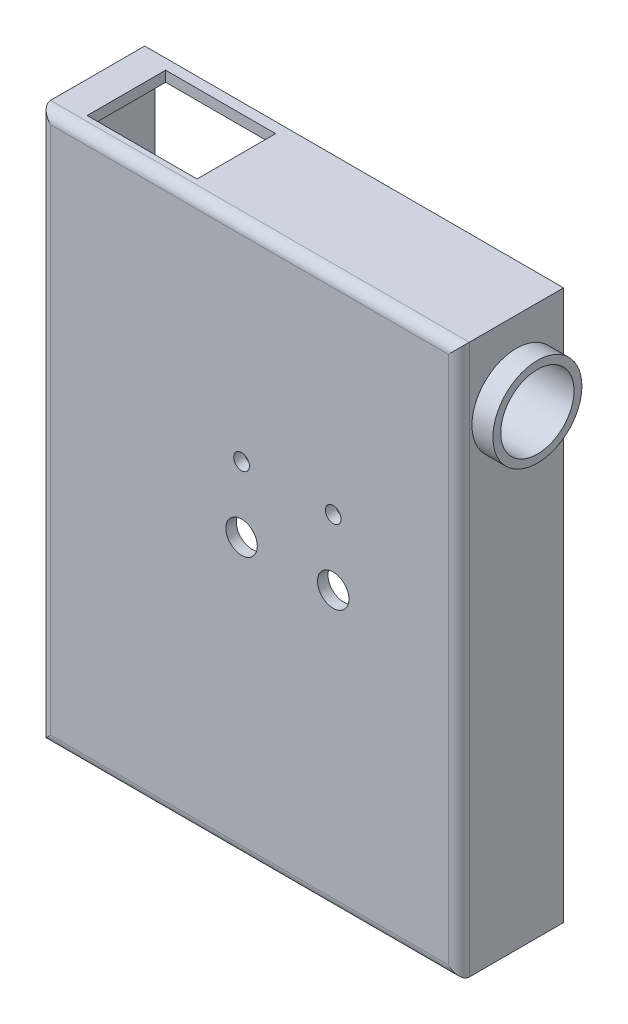
SolidWorks part; units mm, degrees
ref_plane "Front Plane" through (0, 0, 0) normal (0, 0, 1) x (1, 0, 0)
ref_plane "Top Plane" through (0, 0, 0) normal (0, 1, 0) x (1, 0, 0)
ref_plane "Right Plane" through (0, 0, 0) normal (1, 0, 0) x (0, 0, -1)
sketch "Sketch1" plane through (0, 0, 0) normal (0, 0, 1) x (1, 0, 0)
  line L9 (1031.5139, -1366.2512) -> (1111.5139, -1366.2512)
  line L10 (1031.5139, -1366.2512) -> (1031.5139, -1471.2512)
  line L11 (1031.5139, -1471.2512) -> (1111.5139, -1471.2512)
  line L12 (1111.5139, -1366.2512) -> (1111.5139, -1471.2512)
  line L13 (1043.5139, -1392.2512) -> (1103.5139, -1392.2512)
  line L14 (1043.5139, -1392.2512) -> (1043.5139, -1467.2512)
  line L15 (1043.5139, -1467.2512) -> (1103.5139, -1467.2512)
  line L16 (1103.5139, -1392.2512) -> (1103.5139, -1467.2512)
  line L17 (1109.5139, -1368.2512) -> (1033.5139, -1368.2512)
  line L18 (1109.5139, -1368.2512) -> (1109.5139, -1469.2512)
  line L19 (1109.5139, -1469.2512) -> (1033.5139, -1469.2512)
  line L20 (1033.5139, -1368.2512) -> (1033.5139, -1469.2512)
  circle A0 centre (1087.5139, -1418.2512) radius 3
  circle A1 centre (1070.0139, -1418.2512) radius 3
  circle A2 centre (1087.5139, -1405.7512) radius 1.5
  circle A3 centre (1070.0139, -1405.7512) radius 1.5
  dimension "D7" = 6
  dimension "D8" = 6
  dimension "D12" = 3
  dimension "D13" = 3
  dimension "D1" = 105
  dimension "D2" = 80
  dimension "D3" = 75
  dimension "D4" = 60
  dimension "D5" = 12
  dimension "D6" = 4
  dimension "D9" = 16
  dimension "D10" = 17.5
  dimension "D11" = 26
  dimension "D14" = 12.5
  dimension "D15" = 12.5
  dimension "D16" = 26
  dimension "D17" = 8
  dimension "D18" = 2
  dimension "D19" = 2
  dimension "D20" = 2
  dimension "D21" = 2
extrude "Boss-Extrude1" add sketch "Sketch1" along normal blind 20 contours L9 L12 L11 L10
extrude "Cut-Extrude4" cut sketch "Sketch1<3>" against normal blind 20 and the other way blind 20 contours A0 | A2 | A3 | A1 region at (1087.5139, -1418.2512, 0)
sketch "Sketch1<3>" plane through (0, 0, 0) normal (0, 0, 1) x (1, 0, 0) same geometry as "Sketch1"
sketch "Sketch2" plane through (0, 0, 0) normal (0, 0, -1) x (-1, 0, 0)
  line L0 (-1111.5139, -1366.2512) -> (-1111.5139, -1471.2512) construction
  line L1 (-1109.5139, -1368.2512) -> (-1033.5139, -1368.2512)
  line L2 (-1109.5139, -1368.2512) -> (-1109.5139, -1469.2512)
  line L3 (-1109.5139, -1469.2512) -> (-1033.5139, -1469.2512)
  line L4 (-1033.5139, -1368.2512) -> (-1033.5139, -1469.2512)
  line L5 (-1031.5139, -1366.2512) -> (-1111.5139, -1366.2512) construction
  line L6 (-1031.5139, -1366.2512) -> (-1031.5139, -1471.2512) construction
  line L7 (-1031.5139, -1471.2512) -> (-1111.5139, -1471.2512) construction
  dimension "D1" = 2
  dimension "D2" = 2
  dimension "D3" = 2
  dimension "D4" = 2
extrude "Cut-Extrude5" cut sketch "Sketch2" against normal blind 18
sketch "Sketch3" plane through (1109.5139, 0, 0) normal (-1, 0, 0) x (0, 0, 1)
  line L0 (0, -1368.2512) -> (0, -1469.2512) construction
  line L1 (18, -1368.2512) -> (0, -1368.2512) construction
  circle A0 centre (9, -1380.2512) radius 6.5
  dimension "D1" = 13
  dimension "D2" = 9
  dimension "D3" = 12
extrude "Cut-Extrude6" cut sketch "Sketch3" against normal blind 18
sketch "Sketch5" plane through (1111.5139, 0, 0) normal (1, 0, 0) x (0, 0, -1)
  circle A0 centre (-9, -1380.2512) radius 8.5
  circle A1 centre (-9, -1380.2512) radius 6.5 construction
  dimension "D1" = 17
  dimension "D2" = 0
  dimension "D3" = 0
extrude "Boss-Extrude2" add sketch "Sketch5" along normal blind 4
sketch "Sketch6" plane through (1109.5139, 0, 0) normal (-1, 0, 0) x (0, 0, 1)
  circle A0 centre (9, -1380.2512) radius 8.5
  circle A1 centre (9, -1380.2512) radius 6.5 construction
  dimension "D1" = 17
  dimension "D2" = 0
extrude "Boss-Extrude3" add sketch "Sketch6" along normal blind 4
sketch "Sketch7" plane through (1115.5139, 0, 0) normal (1, 0, 0) x (0, 0, -1)
  circle A0 centre (-9, -1380.2512) radius 7
  circle A3 centre (-9, -1380.2512) radius 8.5 construction
  dimension "D1" = 14
  dimension "D2" = 0
extrude "Cut-Extrude7" cut sketch "Sketch7" against normal blind 24
sketch "Sketch8" plane through (0, 0, 18) normal (0, 0, -1) x (-1, 0, 0)
  line L0 (-1033.5139, -1368.2512) -> (-1109.5139, -1368.2512) construction
  line L1 (-1102.0139, -1388.2512) -> (-1072.0139, -1388.2512)
  line L2 (-1102.0139, -1388.2512) -> (-1102.0139, -1389.7512)
  line L3 (-1102.0139, -1389.7512) -> (-1072.0139, -1389.7512)
  line L4 (-1072.0139, -1388.2512) -> (-1072.0139, -1389.7512)
  line L5 (-1109.5139, -1368.2512) -> (-1109.5139, -1469.2512) construction
  dimension "D1" = 20
  dimension "D2" = 1.5
  dimension "D3" = 7.5
  dimension "D4" = 30
extrude "Boss-Extrude4" add sketch "Sketch8" along normal blind 14
sketch "Sketch9" plane through (0, -1469.2512, 0) normal (0, 1, 0) x (1, 0, 0)
  line L0 (1109.5139, 0) -> (1033.5139, 0) construction
  line L1 (1109.5139, -18) -> (1109.5139, 0) construction
  circle A0 centre (1071.5139, 0) radius 2.5
  dimension "D2" = 5
  dimension "D1" = 0
  dimension "D3" = 38
extrude "Cut-Extrude8" cut sketch "Sketch9" against normal blind 14
sketch "Sketch10" plane through (0, -1366.2512, 0) normal (0, 1, 0) x (1, 0, 0)
  line L0 (1031.5139, -20) -> (1031.5139, 0) construction
  line L1 (1058.5139, -2) -> (1037.5139, -2)
  line L2 (1058.5139, -2) -> (1058.5139, -17)
  line L3 (1058.5139, -17) -> (1037.5139, -17)
  line L4 (1037.5139, -2) -> (1037.5139, -17)
  line L5 (1031.5139, -20) -> (1111.5139, -20) construction
  dimension "D1" = 15
  dimension "D2" = 21
  dimension "D3" = 6
  dimension "D4" = 3
extrude "Cut-Extrude9" cut sketch "Sketch10" against normal blind 14
fillet "Fillet1" radius 2 4 edges at (1031.5139, -1418.7512, 20) (1071.5139, -1471.2512, 20) (1111.5139, -1418.7512, 20) (1071.5139, -1366.2512, 20)
sketch "Sketch11" plane through (0, 0, 18) normal (0, 0, -1) x (-1, 0, 0)
  line L0 (-1109.5139, -1469.2512) -> (-1033.5139, -1469.2512) construction
  line L1 (-1033.5139, -1469.2512) -> (-1033.5139, -1368.2512) construction
  circle A0 centre (-1039.5139, -1419.2512) radius 3
  dimension "D2" = 6
  dimension "D1" = 50
  dimension "D3" = 6
extrude "Boss-Extrude5" add sketch "Sketch11" along normal blind 20
hole_wizard "Tap Drill for #4-40 Tap2" positions "Sketch14" profile "Sketch15" hole size "#4-40" standard "ANSI Inch"
sketch "Sketch14" plane through (0, 0, -2) normal (0, 0, -1) x (-1, 0, 0)
  point P0 (-1039.4263, -1419.2825)
sketch "Sketch15" plane through (1039.4263, -1419.2825, -2) normal (1, 0, 0) x (0, 1, 0)
  line L0 (0, 0) -> (0, 13.7292)
  line L1 (0, 13.7292) -> (1.1303, 13.05)
  line L2 (1.1303, 13.05) -> (1.1303, 0)
  line L5 (1.1303, 0) -> (0, 0)
  line L10 (0, 13.7292) -> (-1.1303, 13.05) construction
  line L11 (0, -6.35) -> (0, 107.95) construction
  dimension "Hole Dia." = 2.2606
  dimension "Hole Depth" = 13.05
  dimension "Drill Angle" = 118
